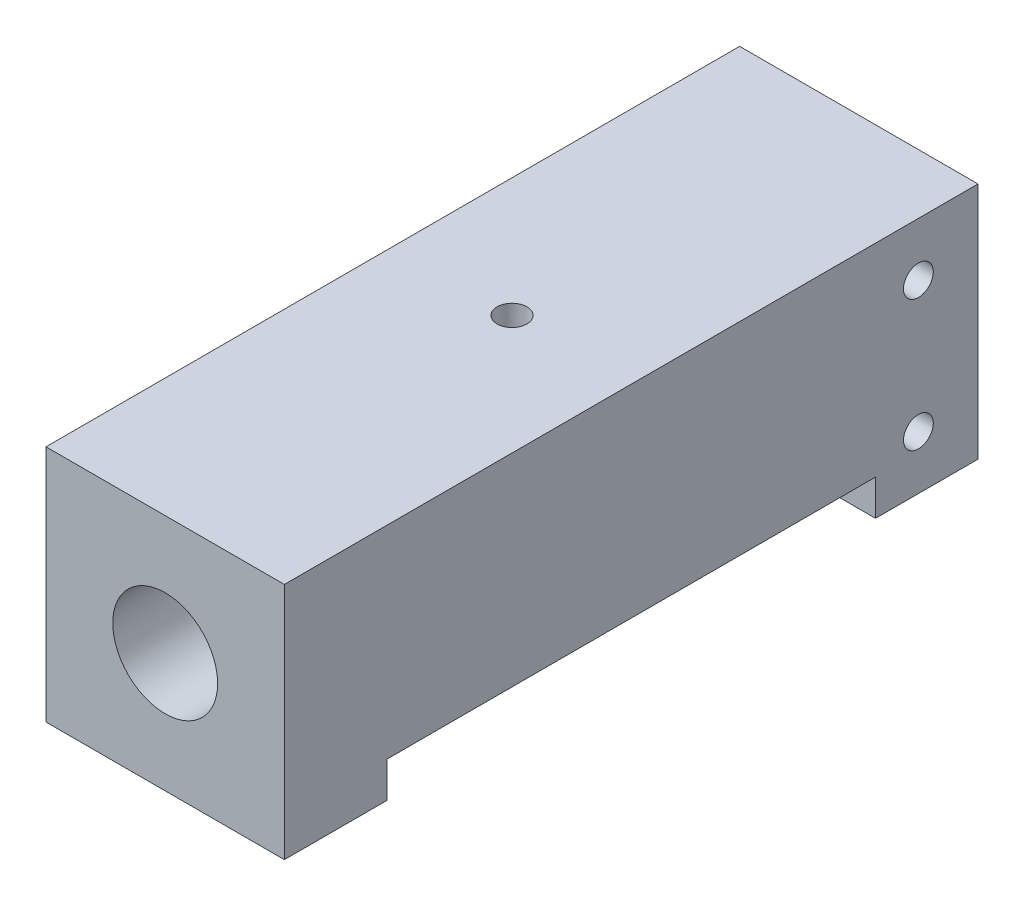
SolidWorks part; units mm, degrees
material "6063-T5"
ref_plane "Piano frontale" through (0, 0, 0) normal (0, 0, 1) x (1, 0, 0)
ref_plane "Piano superiore" through (0, 0, 0) normal (0, 1, 0) x (1, 0, 0)
ref_plane "Piano destro" through (0, 0, 0) normal (1, 0, 0) x (0, 0, -1)
sketch "Schizzo1" plane through (0, 0, 0) normal (0, 0, 1) x (1, 0, 0)
  line L1 (10, -10) -> (-10, -10)
  line L2 (10, -10) -> (10, 10)
  line L3 (10, 10) -> (-10, 10)
  line L4 (-10, -10) -> (-10, 10)
  line L5 (10, -10) -> (-10, 10) construction
  line L6 (10, 10) -> (-10, -10) construction
  point P0 (0, 0)
  dimension "D1" = 20
  dimension "D2" = 20
extrude "Estrusione-Estrusione1" add sketch "Schizzo1" against normal blind 58.2
sketch "Schizzo2" plane through (0, 0, -58.2) normal (0, 0, -1) x (-1, 0, 0)
  circle A0 centre (0, 0) radius 3
  dimension "D1" = 6
extrude "Taglio-Estrusione1" cut sketch "Schizzo2" against normal through all
sketch "Schizzo3" plane through (0, 0, -58.2) normal (0, 0, -1) x (-1, 0, 0)
  point P0 (0, 0)
hole_wizard "Foro filettato G1/8-1" positions "Schizzo8" profile "Schizzo7" tap size "G1/8" standard "BSI"
sketch "Schizzo8" plane through (0, 0, 0) normal (0, 0, 1) x (1, 0, 0)
  point P0 (0, 0)
sketch "Schizzo7" plane through (0, 0, 0) normal (1, 0, 0) x (0, -1, 0)
  line L0 (0, 0) -> (0, 12.6438)
  line L1 (0, 12.6438) -> (4.4, 10)
  line L2 (4.4, 10) -> (4.4, 0)
  line L5 (4.4, 0) -> (0, 0)
  line L10 (0, 12.6438) -> (-4.4, 10) construction
  line L11 (0, -6.35) -> (0, 107.95) construction
  dimension "Tap Drill Dia." = 8.8
  dimension "Tap Drill Depth" = 10
  dimension "Drill Angle" = 118
sketch "Schizzo11" plane through (0, 10, 0) normal (0, 1, 0) x (1, 0, 0)
  line L0 (0, 58.2) -> (0, 0) construction
  line L1 (10, 58.2) -> (-10, 58.2) construction
  line L2 (10, 29.1) -> (-10, 29.1) construction
  line L3 (10, 58.2) -> (10, 0) construction
  point P10 (0, 29.1)
  point P11 (0, 29.1)
  point P12 (0, 29.1)
hole_wizard "M3 Tapped Hole2" positions "Schizzo3D1" profile "Schizzo12" tap size "M3" standard "DIN"
sketch3d "Schizzo3D1"
  point P0 (0, 10, -29.1)
sketch "Schizzo12" plane through (0, 10, -29.1) normal (1, 0, 0) x (0, 0, 1)
  line L0 (0, 0) -> (0, 5.7511)
  line L1 (0, 5.7511) -> (1.25, 5)
  line L2 (1.25, 5) -> (1.25, 0)
  line L5 (1.25, 0) -> (0, 0)
  line L10 (0, 5.7511) -> (-1.25, 5) construction
  line L11 (0, -6.35) -> (0, 107.95) construction
  dimension "Tap Drill Dia." = 2.5
  dimension "Tap Drill Depth" = 5
  dimension "Drill Angle" = 118
cosmetic thread "Hole Thread4" parameters "D1"=5, "D2"=3
hole_wizard "Foro Ø16.0 (16)-1" positions "Schizzo3D3" profile "Schizzo14" hole size "Ø16.0" standard "ISO"
sketch3d "Schizzo3D3"
  point P0 (0, 0, 0)
  point P3 (0, 0, -58.2)
sketch "Schizzo14" plane through (0, 0, -58.2) normal (1, 0, 0) x (0, 1, 0)
  line L0 (0, 0) -> (0, 16.8069)
  line L1 (0, 16.8069) -> (8, 12)
  line L2 (8, 12) -> (8, 0)
  line L5 (8, 0) -> (0, 0)
  line L10 (0, 16.8069) -> (-8, 12) construction
  line L11 (0, -6.35) -> (0, 107.95) construction
  dimension "Hole Dia." = 16
  dimension "Hole Depth" = 12
  dimension "Drill Angle" = 118
sketch "Schizzo15" plane through (10, 0, 0) normal (1, 0, 0) x (0, 0, -1)
  line L0 (46.2, 0) -> (58.2, 0) construction
  line L1 (46.2, 8) -> (46.2, -8) construction
  line L4 (58.2, -10) -> (58.2, 10) construction
  line L6 (58.2, -10) -> (0, -10) construction
  point P5 (53.2, -5.5)
  point P8 (53.2, 5.5)
  dimension "D1" = 5.5
  dimension "D2" = 7
  dimension "D3" = 5
  dimension "D4" = 4.5
hole_wizard "Foro filettato M3-2" positions "Schizzo3D4" profile "Schizzo16" tap size "M3" standard "ISO" end condition through all
sketch3d "Schizzo3D4"
  point P0 (10, 5.5, -53.2)
  point P3 (10, -5.5, -53.2)
sketch "Schizzo16" plane through (10, 5.5, -53.2) normal (0, 1, 0) x (0, 0, -1)
  line L0 (0, 0) -> (0, 20)
  line L1 (0, 20) -> (1.25, 20)
  line L2 (1.25, 20) -> (1.25, 0)
  line L5 (1.25, 0) -> (0, 0)
  line L11 (0, -6.35) -> (0, 107.95) construction
  dimension "Thread Major Dia." = 2.5
  dimension "Thru Tap Drill Depth" = 20
sketch "Sketch1" plane through (-10, 0, 0) normal (-1, 0, 0) x (0, 0, 1)
  line L0 (-58.2, 10) -> (-58.2, -10) construction
  line L1 (-58.2, 3) -> (-22, 3)
  line L2 (-58.2, 3) -> (-58.2, -3)
  line L3 (-58.2, -3) -> (-22, -3)
  line L4 (-22, 3) -> (-22, -3)
  line L5 (0, 10) -> (0, -10) construction
  line L6 (0, 0) -> (-22, 0) construction
  point P8 (-22, 0)
  dimension "D1" = 6
  dimension "D2" = 22
extrude "Boss-Extrude1" add sketch "Sketch1" along normal blind 4.9
sketch "Sketch2" plane through (10, 0, 0) normal (1, 0, 0) x (0, 0, -1)
  line L0 (58.2, -10) -> (0, -10) construction
  line L1 (49.6, -10) -> (33.6, -10)
  line L2 (49.6, -10) -> (49.6, -7)
  line L3 (49.6, -7) -> (33.6, -7)
  line L4 (33.6, -7) -> (8.6, -7)
  line L5 (41.6, -7) -> (41.6, -13) construction
  line L6 (8.6, -7) -> (8.6, -10)
  line L7 (8.6, -10) -> (33.6, -10)
  line L8 (0, -10) -> (8.6, -10) construction
  line L9 (49.6, -10) -> (58.2, -10) construction
  circle A2 centre (41.6, -13) radius 4 construction
  dimension "D1" = 16
  dimension "D2" = 3
extrude "Cut-Extrude1" cut sketch "Sketch2" against normal through all
